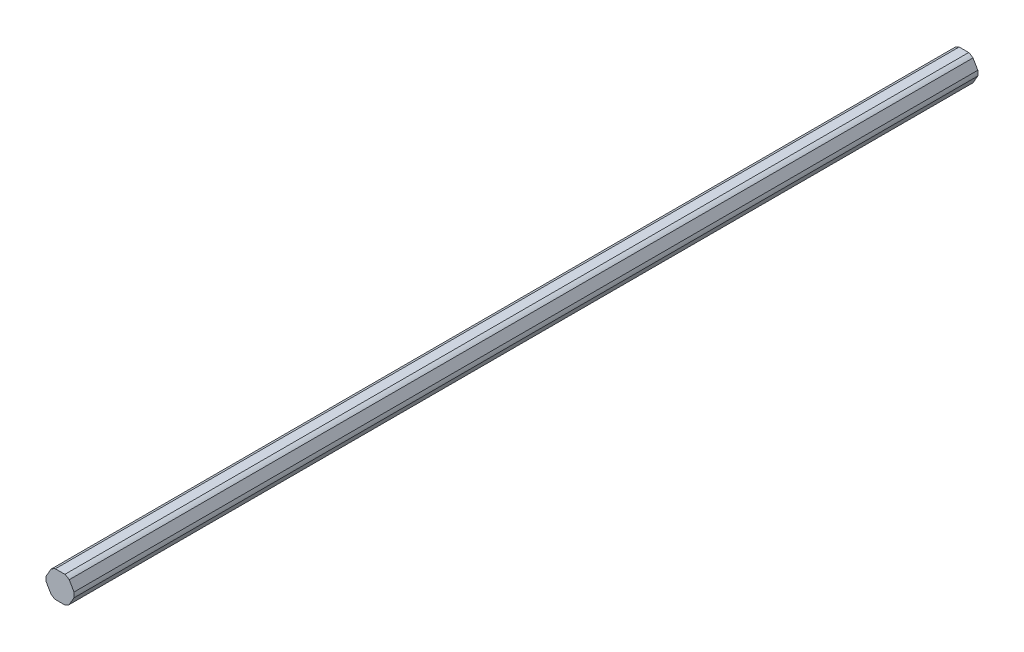
SolidWorks part; units mm, degrees
ref_plane "Front Plane" through (0, 0, 0) normal (0, 0, 1) x (1, 0, 0)
ref_plane "Top Plane" through (0, 0, 0) normal (0, 1, 0) x (1, 0, 0)
ref_plane "Right Plane" through (0, 0, 0) normal (1, 0, 0) x (0, 0, -1)
sketch "Sketch1" plane through (0, 0, 0) normal (0, 0, 1) x (1, 0, 0)
  line L1 (-7.3323, 0) -> (-3.6662, -6.35)
  line L2 (-3.6662, -6.35) -> (3.6662, -6.35)
  line L3 (3.6662, -6.35) -> (7.3323, 0)
  line L4 (7.3323, 0) -> (3.6662, 6.35)
  line L5 (3.6662, 6.35) -> (-3.6662, 6.35)
  line L6 (-3.6662, 6.35) -> (-7.3323, 0)
  circle A1 centre (0, 0) radius 6.35 construction
  circle A2 centre (0, 0) radius 6.75
  dimension "D2" = 13.5
  dimension "D1" = 12.7
extrude "Boss-Extrude1" add sketch "Sketch1" along normal blind 431.8 contours L4 A2 L5 L6 L1 L2 L3 region at (0, 0, 0)
ref_plane "Plane1" through (0, 0, 215.9) normal (0, 0, 1) x (1, 0, 0)
